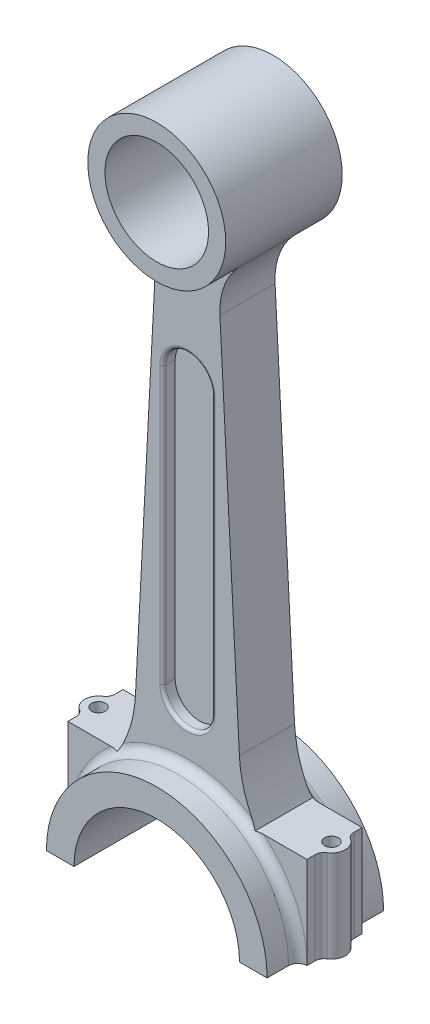
SolidWorks part; units mm, degrees
material "7075-T6, Plate (SS)"
ref_plane "Front Plane" through (0, 0, 0) normal (0, 0, 1) x (1, 0, 0)
ref_plane "Top Plane" through (0, 0, 0) normal (0, 1, 0) x (1, 0, 0)
ref_plane "Right Plane" through (0, 0, 0) normal (1, 0, 0) x (0, 0, -1)
sketch "Sketch1" plane through (0, 0, 0) normal (0, 0, 1) x (1, 0, 0)
  line L0 (0, 0) -> (32835.0999, 0) construction
  line L1 (0, 0) -> (0, 32835.0999) construction
  line L2 (39, 30) -> (22.4835, 30)
  line L3 (10, 181.0444) -> (16.9576, 48.2859)
  line L4 (-39, 30) -> (-39, 0)
  line L5 (39, 30) -> (39, 0)
  line L6 (39, 0) -> (0, 0)
  line L7 (-39, 30) -> (-22.4835, 30)
  line L8 (-10, 181.0444) -> (-16.9576, 48.2859)
  line L9 (-27, 0) -> (-39, 0)
  line L10 (-22.4835, 30) -> (-19.8997, 30)
  line L11 (22.4835, 30) -> (19.8997, 30)
  circle A0 centre (0, 201.2) radius 22.5
  circle A1 centre (0, 201.2) radius 16.9
  arc A2 (16.9576, 48.2859) -> (22.4835, 30) centre (56.9028, 50.3793) ccw
  arc A3 (-16.9576, 48.2859) -> (-22.4835, 30) centre (-56.9028, 50.3793) cw
  arc A4 (36, 0) -> (-36, 0) centre (0, 0) ccw
  arc A5 (27, 0) -> (-27, 0) centre (0, 0) ccw
  dimension "D2" = 33.8
  dimension "D3" = 45
  dimension "D6" = 40
  dimension "D8" = 36
  dimension "D9" = 27
  dimension "D5" = 3
  dimension "D7" = 30
  dimension "D10" = 201.2
  dimension "D11" = 20
  dimension "D12" = 3
extrude "Boss-Extrude1" add sketch "Sketch1" along normal mid plane 18 contours A4 L11 A2 L3 A0 L8 A3 L10 | A4 L6 L5 L2 L11 | A4 L10 L7 L4 L9 region at (33.7763, 19.8358, 0) region at (0, 99.5269, 0) region at (-33.7763, 19.8358, 0)
extrude "Boss-Extrude2" add sketch "Sketch1<3>" along normal mid plane 38 contours A5 L6 A4 L9 | A0 A1 region at (31.0113, 16.643, 0) region at (0, 179.3364, 0)
sketch "Sketch1<3>" plane through (0, 0, 0) normal (0, 0, 1) x (1, 0, 0) same geometry as "Sketch1"
fillet "Fillet1" radius 22.5 2 edges at (10, 181.0444, 0) (-10, 181.0444, 0)
fillet "Fillet2" radius 3 2 edges at (0, 36, -9) (0, 36, 9)
sketch "Sketch2" plane through (0, 0, 9) normal (0, 0, 1) x (1, 0, 0)
  line L0 (0, 0) -> (0, 50000) construction
  line L1 (0, 0) -> (50000, 0) construction
  line L2 (0, 145.6) -> (0, 55.6) construction
  line L3 (8, 145.6) -> (8, 55.6)
  line L4 (-8, 145.6) -> (-8, 55.6)
  line L5 (0, 201.2) -> (0, 0) construction
  arc A0 (8, 145.6) -> (-8, 145.6) centre (0, 145.6) ccw
  arc A1 (-8, 55.6) -> (8, 55.6) centre (0, 55.6) ccw
  circle A2 centre (0, 201.2) radius 16.9 construction
  circle A3 centre (0, 201.2) radius 16.9 construction
  arc A4 (27, 0) -> (-27, 0) centre (0, 0) ccw construction
  arc A5 (27, 0) -> (-27, 0) centre (0, 0) ccw construction
  point P7 (0, 100.6)
  point P12 (0, 100.6)
  dimension "D2" = 8
  dimension "D1" = 90
extrude "Cut-Extrude1" cut sketch "Sketch2" against normal blind 4
mirror "Mirror1" about plane through (0, 0, 0) normal (0, 0, 1) of "Cut-Extrude1"
fillet "Fillet3" radius 1 8 edges at (8, 100.6, 9) (0, 47.6, 9) (-8, 100.6, 9) (0, 47.6, -9) (-8, 100.6, -9) (0, 153.6, -9) (0, 153.6, 9) (8, 100.6, -9)
sketch "Sketch4" plane through (0, 0, 0) normal (0, 1, 0) x (1, 0, 0)
  line L0 (0, 0) -> (0, -23.3408) construction
  circle A0 centre (-38, 0) radius 4.5
  circle A1 centre (38, 0) radius 4.5
  circle A2 centre (-38, 0) radius 2.25
  circle A3 centre (38, 0) radius 2.25
  dimension "D2" = 9
  dimension "D3" = 4.5
  dimension "D1" = 76
extrude "Boss-Extrude3" add sketch "Sketch4" along normal blind 30
fillet "Fillet4" radius 3 4 edges at (39, 15, -4.3875) (39, 15, 4.3875) (-39, 15, -4.3875) (-39, 15, 4.3875)
extrude "Cut-Extrude2" cut sketch "Sketch4<3>" along normal up to next contours A2 | A3 region at (-38, 0, 0) region at (38, 0, 0)
sketch "Sketch4<3>" plane through (0, 0, 0) normal (0, 1, 0) x (1, 0, 0) same geometry as "Sketch4"
